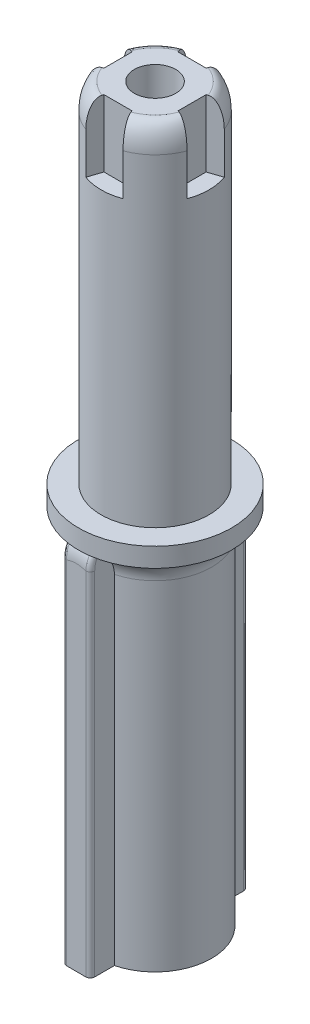
SolidWorks part; units mm, degrees
ref_plane "Спереди" through (0, 0, 0) normal (0, 0, 1) x (1, 0, 0)
ref_plane "Сверху" through (0, 0, 0) normal (0, 1, 0) x (1, 0, 0)
ref_plane "Справа" through (0, 0, 0) normal (1, 0, 0) x (0, 0, -1)
sketch "Эскиз1" plane through (0, 0, 0) normal (1, 0, 0) x (0, 0, -1)
  line L0 (0, 0) -> (0, 114.6)
  line L1 (0, 114.6) -> (8.45, 114.6)
  line L2 (8.45, 114.6) -> (8.45, 60)
  line L3 (8.45, 60) -> (12, 60)
  line L4 (12, 60) -> (12, 0)
  line L5 (12, 0) -> (0, 0)
  dimension "D1" = 12
  dimension "D2" = 8.45
  dimension "D3" = 60
  dimension "D4" = 54.6
revolve "Повернуть1" add sketch "Эскиз1" angle 360 about L0
sketch "Эскиз3" plane through (0, 114.6, 0) normal (0, 1, 0) x (1, 0, 0)
  line L0 (0, 0) -> (0, 5.8) construction
  line L1 (-2.2, 5.8) -> (-2.9319, 7.9784)
  line L2 (2.2, 5.8) -> (2.9319, 7.9784)
  line L3 (-2.2, 5.8) -> (2.2, 5.8)
  line L14 (5.8, 2.2) -> (5.8, -2.2)
  line L15 (5.8, -2.2) -> (7.9784, -2.9319)
  line L16 (5.8, 2.2) -> (7.9784, 2.9319)
  line L17 (2.2, -5.8) -> (-2.2, -5.8)
  line L18 (-2.2, -5.8) -> (-2.9319, -7.9784)
  line L19 (2.2, -5.8) -> (2.9319, -7.9784)
  line L20 (-5.8, -2.2) -> (-5.8, 2.2)
  line L21 (-5.8, 2.2) -> (-7.9784, 2.9319)
  line L22 (-5.8, -2.2) -> (-7.9784, -2.9319)
  arc A0 (2.9319, 7.9784) -> (-2.9319, 7.9784) centre (0, 0) ccw
  arc A1 (7.9784, -2.9319) -> (7.9784, 2.9319) centre (0, 0) ccw
  arc A2 (-2.9319, -7.9784) -> (2.9319, -7.9784) centre (0, 0) ccw
  arc A3 (-7.9784, 2.9319) -> (-7.9784, -2.9319) centre (0, 0) ccw
  point P22 (0, 0)
  point P25 (0, 0)
  dimension "D4" = 17
  dimension "D1" = 5.8
  dimension "D2" = 4
  dimension "D3" = 37.141
  dimension "D7" = 4.4
extrude "Вырез-Вытянуть1" cut sketch "Эскиз3" against normal blind 10.5
sketch "Эскиз4" plane through (0, 0, 0) normal (0, -1, 0) x (1, 0, 0)
  circle A0 centre (0, 0) radius 13.9436
  circle A1 centre (0, 0) radius 8.85
  dimension "D1" = 17.7
extrude "Вырез-Вытянуть2" cut sketch "Эскиз4" against normal blind 57
fillet "Скругление1" radius 4 1 edges at (0, 57, -8.85)
sketch "Эскиз5" plane through (0, 0, 0) normal (0, -1, 0) x (1, 0, 0)
  line L0 (0, 8.85) -> (0, 12.35) construction
  line L1 (-2.2, -12.35) -> (2.2, -12.35)
  line L2 (-2.2, -12.35) -> (-2.2, 12.35)
  line L3 (-2.2, 12.35) -> (2.2, 12.35)
  line L4 (2.2, -12.35) -> (2.2, 12.35)
  line L5 (-2.2, -12.35) -> (2.2, 12.35) construction
  line L6 (-2.2, 12.35) -> (2.2, -12.35) construction
  circle A0 centre (0, 0) radius 8.85 construction
  circle A1 centre (0, 0) radius 8.85 construction
  point P0 (0, 0)
  dimension "D1" = 3.5
  dimension "D2" = 4.4
extrude "Бобышка-Вытянуть1" add sketch "Эскиз5" against normal blind 57
fillet "Скругление2" radius 4 2 edges at (0, 57, 12.35) (0, 57, -12.35)
fillet "Скругление3" radius 0.7 8 edges at (-2.2, 55.6345, -12.2803) (2.2, 56.3378, -12.0955) (2.2, 55.6345, 12.2803) (-2.2, 56.3378, 12.0955) (-2.2, 27.4187, -12.35) (2.2, 27.4187, -12.35) (2.2, 27.4187, 12.35) (-2.2, 27.4187, 12.35)
sketch "Эскиз6" plane through (0, 114.6, 0) normal (0, 1, 0) x (1, 0, 0)
  circle A0 centre (0, 0) radius 3.25
  dimension "D1" = 6.5
extrude "Вырез-Вытянуть3" cut sketch "Эскиз6" against normal blind 7.6
sketch "Эскиз7" plane through (0, 0, 0) normal (0, -1, 0) x (1, 0, 0)
  circle A0 centre (0, 0) radius 3.25
  dimension "D1" = 6.5
extrude "Вырез-Вытянуть4" cut sketch "Эскиз7" against normal blind 7.6
fillet "Скругление4" radius 2 4 edges at (-5.9751, 114.6, 5.9751) (-5.9751, 114.6, -5.9751) (5.9751, 114.6, -5.9751) (5.9751, 114.6, 5.9751) second distance 4 first distance on face at (0, 114.6, 3.25)
